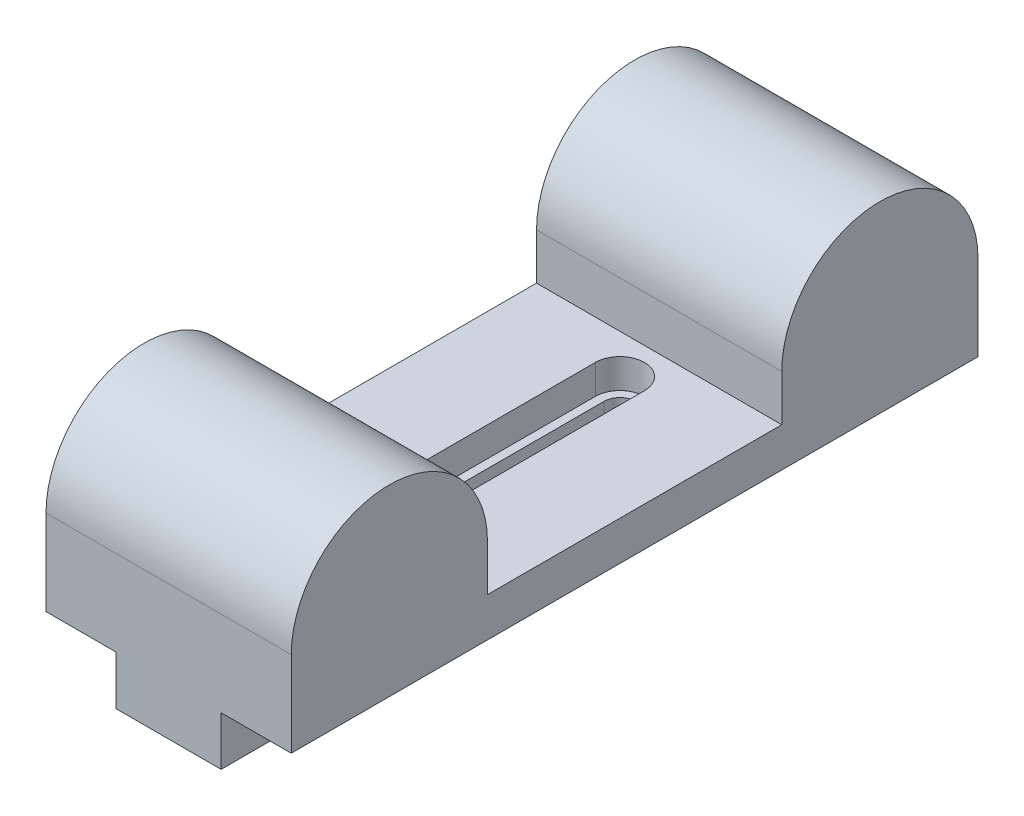
SolidWorks part; units mm, degrees
material "Alloy Steel"
ref_plane "Front Plane" through (0, 0, 0) normal (0, 0, 1) x (1, 0, 0)
ref_plane "Top Plane" through (0, 0, 0) normal (0, 1, 0) x (1, 0, 0)
ref_plane "Right Plane" through (0, 0, 0) normal (1, 0, 0) x (0, 0, -1)
sketch "Sketch1" plane through (0, 0, 0) normal (1, 0, 0) x (0, 0, -1)
  line L0 (10, 18.7) -> (60, 18.7) construction
  line L1 (0, 0) -> (70, 0)
  line L2 (0, 0) -> (0, 4)
  line L3 (0, 4) -> (70, 4)
  line L4 (70, 0) -> (70, 4)
  line L5 (91.0428, 29.2) -> (-12.4001, 29.2) construction
  line L6 (0, 4) -> (0, 8.7)
  line L7 (20, 8.7) -> (20, 4)
  line L9 (50, 8.7) -> (50, 4)
  line L11 (70, 8.7) -> (70, 4)
  arc A0 (0, 8.7) -> (20, 8.7) centre (10, 8.7) cw
  arc A3 (50, 8.7) -> (70, 8.7) centre (60, 8.7) cw
  point P24 (10, 18.7)
  dimension "D1" = 4
  dimension "D2" = 10.5
  dimension "D3" = 29.2
  dimension "D4" = 50
  dimension "D5" = 70
extrude "Boss-Extrude1" add sketch "Sketch1" along normal mid plane 25 contours A0 L3 | L1 L4 L3 L2 | L3 region at (0, 2, -35) region at (0, 10.4754, -10) region at (0, 10.4754, -60)
sketch "Sketch2" plane through (0, 0, 0) normal (0, 1, 0) x (1, 0, 0)
  line L0 (12.5, 0) -> (-12.5, 0) construction
  line L1 (-5.35, 0) -> (5.35, 0)
  line L2 (-5.35, 0) -> (-5.35, 41.65)
  line L3 (-5.35, 41.65) -> (5.35, 41.65)
  line L4 (5.35, 0) -> (5.35, 41.65)
  arc A0 (-5.35, 41.65) -> (5.35, 41.65) centre (0, 41.65) cw
  point P8 (0, 0)
  point P9 (0, 0)
  dimension "D2" = 47
  dimension "D1" = 10.7
extrude "Boss-Extrude2" add sketch "Sketch2" against normal blind 5 contours A0 L3 | L1 L4 L3 L2 region at (0, 0, -20.825) region at (0, 0, -43.9206)
sketch "Sketch4" plane through (0, 0, 0) normal (0, 1, 0) x (1, 0, 0)
  line L0 (0, 0) -> (0, 46) construction
  line L1 (0, 46) -> (0, 40) construction
  line L2 (2.5, 46) -> (2.5, 40)
  line L3 (-2.5, 46) -> (-2.5, 40)
  line L4 (0, 31) -> (0, 25) construction
  line L5 (2.5, 31) -> (2.5, 25)
  line L6 (-2.5, 31) -> (-2.5, 25)
  line L7 (1.625, 46) -> (1.625, 40)
  line L8 (-1.625, 46) -> (-1.625, 40)
  line L9 (1.625, 31) -> (1.625, 25)
  line L10 (-1.625, 31) -> (-1.625, 25)
  line L12 (-2.5, 40) -> (2.5, 40)
  line L13 (-2.5, 40) -> (-2.5, 31)
  line L14 (-2.5, 31) -> (2.5, 31)
  line L15 (2.5, 40) -> (2.5, 31)
  line L16 (-1.625, 40) -> (1.625, 40)
  line L17 (-1.625, 40) -> (-1.625, 31)
  line L18 (-1.625, 31) -> (1.625, 31)
  line L19 (1.625, 40) -> (1.625, 31)
  arc A0 (2.5, 46) -> (-2.5, 46) centre (0, 46) ccw
  arc A1 (-2.5, 40) -> (2.5, 40) centre (0, 40) ccw
  arc A2 (2.5, 31) -> (-2.5, 31) centre (0, 31) ccw
  arc A3 (-2.5, 25) -> (2.5, 25) centre (0, 25) ccw
  arc A4 (-1.625, 40) -> (1.625, 40) centre (0, 40) ccw
  arc A5 (1.625, 46) -> (-1.625, 46) centre (0, 46) ccw
  arc A6 (-1.625, 25) -> (1.625, 25) centre (0, 25) ccw
  arc A7 (1.625, 31) -> (-1.625, 31) centre (0, 31) ccw
  point P3 (0, 43)
  point P9 (0, 28)
  dimension "D1" = 5
  dimension "D2" = 6
  dimension "D3" = 15
  dimension "D4" = 46
  dimension "D5" = 3.25
extrude "Cut-Extrude1" cut sketch "Sketch4" against normal through all both and the other way through all contours L7 A5 L8 L12 | A4 L17 A1 L19 | L12 A4 | A2 L19 A1 L17 | A7 L19 A2 L17 | L14 A7 | L10 A6 L9 L14 region at (0, 0, -43.6472) region at (0, 0, -39.3103) region at (0, 0, -38.2553) region at (0, 0, -35.5) region at (0, 0, -27.3528) region at (0, 0, -32.7447) region at (0, 0, -31.6897)
extrude "Cut-Extrude2" cut sketch "Sketch4<3>" against normal blind 3 from surface contours A6 L10 L14 L6 A3 L5 L9 | L17 A2 L14 | A2 L17 A1 L13 | L14 A2 L19 | A2 L15 A1 L19 | L19 A1 L12 | A5 L7 L12 L2 A0 L3 L8 | L12 A1 L17 region at (2.4014, 0, -43) region at (1.9808, 0, -39.2674) region at (2.0963, 0, -35.5) region at (2.4014, 0, -28) region at (1.9808, 0, -31.7326) region at (-2.0963, 0, -35.5) region at (-1.9808, 0, -39.2674) region at (-1.9808, 0, -31.7326) starting at face at (0, 4, -35)
sketch "Sketch4<3>" plane through (0, 0, 0) normal (0, 1, 0) x (1, 0, 0) same geometry as "Sketch4"
